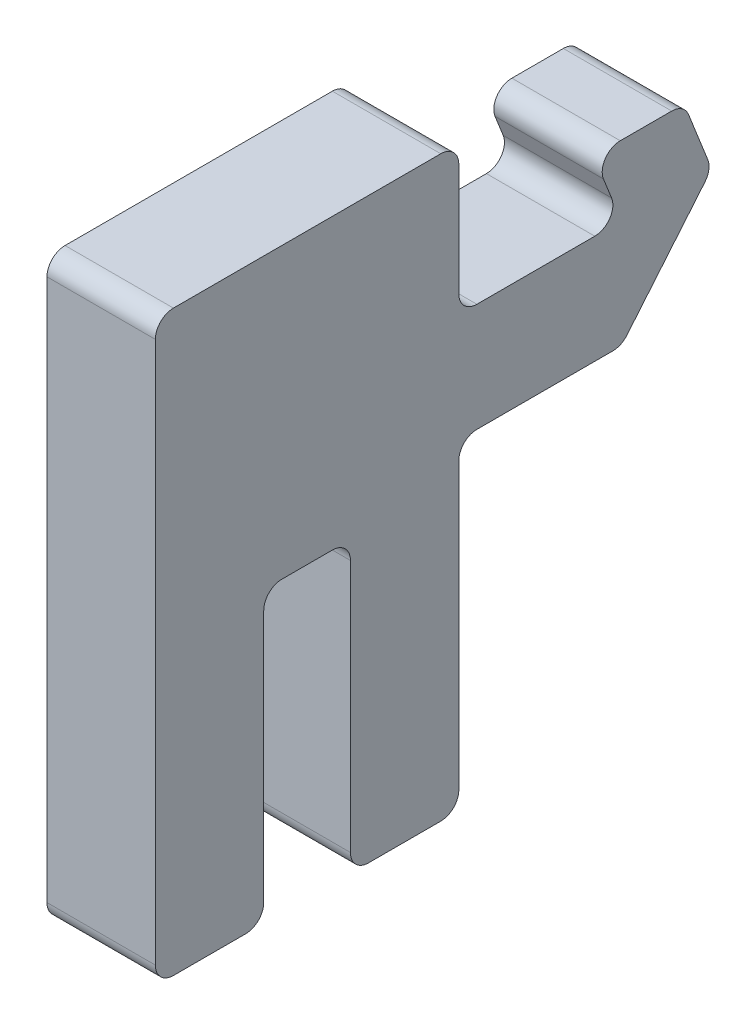
SolidWorks part; units mm, degrees
ref_plane "Alzado" through (0, 0, 0) normal (0, 0, 1) x (1, 0, 0)
ref_plane "Planta" through (0, 0, 0) normal (0, 1, 0) x (1, 0, 0)
ref_plane "Vista lateral" through (0, 0, 0) normal (1, 0, 0) x (0, 0, -1)
sketch "Croquis1" plane through (0, 0, 0) normal (1, 0, 0) x (0, 0, -1)
  line L1 (-4.2, 8) -> (4.2, 8)
  line L2 (-4.2, 8) -> (-4.2, -8)
  line L3 (-4.2, -8) -> (4.2, -8)
  line L16 (4.2, 8) -> (4.2, -8)
  dimension "D1" = 4.2
  dimension "D2" = 8
  dimension "D3" = 16
  dimension "D4" = 8.4
extrude "Saliente-Extruir1" add sketch "Croquis1" along normal blind 3
sketch "Croquis2" plane through (3, 0, 0) normal (1, 0, 0) x (0, 0, -1)
  line L0 (0, 0) -> (0, -9.3656) construction
  line L1 (-4.2, -8) -> (4.2, -8) construction
  line L2 (-1.2, -8) -> (1.2, -8)
  line L3 (-1.2, -8) -> (-1.2, 0)
  line L4 (-1.2, 0) -> (1.2, 0)
  line L5 (1.2, -8) -> (1.2, 0)
  dimension "D1" = 1.2
  dimension "D2" = 1.2
  dimension "D3" = 8
extrude "Cortar-Extruir1" cut sketch "Croquis2" against normal up to surface (3 mm away) up to face at (0, 0, 0)
sketch "Croquis4" plane through (3, 0, 0) normal (1, 0, 0) x (0, 0, -1)
  line L9 (1.2, 0) -> (-1.2, 0) construction
  line L10 (0, 0) -> (0, 10.8389) construction
  line L18 (4.2, 3.8918) -> (4.2, 0.8918)
  line L19 (4.2, -8) -> (4.2, 8) construction
  line L20 (4.2, 0.8918) -> (8.7, 0.8918)
  line L22 (8.7, 3.8918) -> (4.2, 3.8918)
  line L25 (7.9325, 5.8274) -> (8.7, 3.8918)
  line L26 (7.9325, 5.8274) -> (10.4325, 5.8274)
  line L27 (10.4325, 5.8274) -> (11.2, 3.8918)
  line L28 (11.2, 3.8918) -> (8.7, 0.8918)
  dimension "D1" = 4.5
  dimension "D2" = 3
  dimension "D3" = 4.5
  dimension "D4" = 3.8918
  dimension "D5" = 5.8274
  dimension "D6" = 6.1126
  dimension "D7" = 2.5
  dimension "D8" = 11.8459
extrude "Saliente-Extruir2" add sketch "Croquis4" against normal up to surface (3 mm away) up to face at (0, -2, 0)
fillet "Redondeo1" radius 0.5 15 edges at (1.5, 8, 4.2) (1.5, 3.8918, -4.2) (1.5, 8, -4.2) (1.5, 5.8274, -7.9325) (1.5, 5.8274, -10.4325) (1.5, 3.8918, -11.2) (1.5, 0.8918, -8.7) (1.5, 0.8918, -4.2) (1.5, 0, -1.2) (1.5, 0, 1.2) (1.5, -8, 1.2) (1.5, -8, 4.2) (1.5, -8, -4.2) (1.5, -8, -1.2) (1.5, 3.8918, -8.7)
